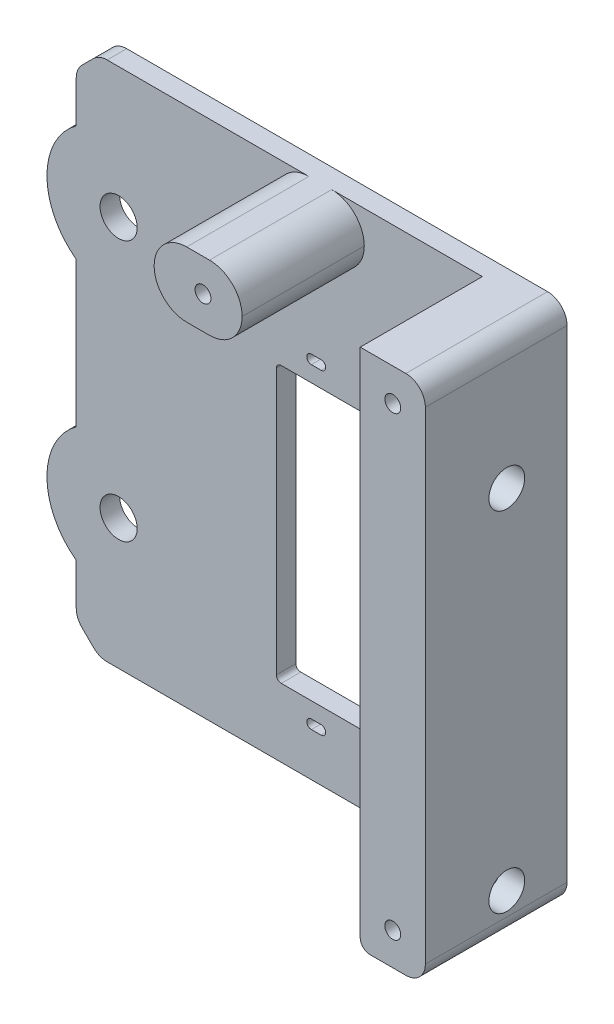
SolidWorks part; units mm, degrees
ref_plane "Front Plane" through (0, 0, 0) normal (0, 0, 1) x (1, 0, 0)
ref_plane "Top Plane" through (0, 0, 0) normal (0, 1, 0) x (1, 0, 0)
ref_plane "Right Plane" through (0, 0, 0) normal (1, 0, 0) x (0, 0, -1)
sketch "Base" plane through (0, 0, 0) normal (0, 0, 1) x (1, 0, 0)
  line L1 (-29.1058, 40) -> (-29.1058, -40)
  line L4 (-17.7758, -40) -> (43.2242, -40)
  line L8 (-22.6058, 20) -> (-22.6058, -20) construction
  line L9 (12.7242, 15.875) -> (12.7242, -32.625) construction
  line L10 (23.8492, 12.75) -> (1.5992, 12.75)
  line L11 (23.8492, 12.75) -> (23.8492, -29.5)
  line L12 (23.8492, -29.5) -> (1.5992, -29.5)
  line L13 (1.5992, 12.75) -> (1.5992, -29.5)
  line L14 (33.2242, 30) -> (33.2242, -30) construction
  line L15 (33.2242, 1) -> (43.2242, 1) construction
  line L16 (43.2242, 40) -> (43.2242, -40)
  line L18 (-17.7758, -40) -> (-29.1058, -40)
  line L19 (33.2242, -30) -> (33.2242, -40) construction
  line L20 (33.2242, 30) -> (43.2242, 40) construction
  line L21 (-29.1058, 40) -> (43.2242, 40)
  line L22 (7.7242, -32.625) -> (17.7242, -32.625)
  line L24 (33.2242, 30) -> (1.5992, 30) construction
  line L25 (1.5992, 30) -> (1.5992, 40) construction
  line L26 (1.5992, -40) -> (1.5992, -30) construction
  line L27 (1.5992, -30) -> (33.2242, -30) construction
  line L28 (7.7242, 15.875) -> (17.7242, 15.875)
  circle A0 centre (12.7242, -20) radius 17.5 construction
  point P2 (30.2242, -20)
  point P7 (24.1741, 0)
  point P9 (12.7242, -40)
  point P10 (-29.1058, 0)
  point P11 (-22.6058, -20)
  point P12 (-22.6058, 20)
  point P15 (-22.6058, 0)
  point P20 (12.7242, 12.75)
  point P22 (23.8492, -8.375)
  point P23 (12.7242, 20)
  point P24 (-22.6058, -20)
  point P25 (-22.6058, 20)
  point P26 (12.7242, 15.875)
  point P27 (12.7242, -32.625)
  point P30 (12.7242, -8.375)
  point P31 (12.7242, -20)
  point P33 (12.7242, -2.5)
  point P41 (38.2242, -35)
  point P43 (38.2242, 35)
  point P44 (9.0992, 35)
  point P45 (1.5992, 35)
  point P46 (38.2242, 1)
  point P47 (33.2242, -35)
  point P48 (7.7242, -32.625)
  point P49 (17.7242, -32.625)
  point P50 (7.7242, 15.875)
  point P51 (17.7242, 15.875)
  dimension "D11" = 35
  dimension "D2" = 42.25
  dimension "D1" = 22.25
  dimension "D4" = 35.33
  dimension "D9" = 48.5
  dimension "D3" = 40
  dimension "D10" = 9.5
  dimension "D5" = 6.5
  dimension "D14" = 10
  dimension "D7" = 80
  dimension "D8" = 10
  dimension "D12" = 3.5
  dimension "D6" = 3
  dimension "D13" = 7.5
  dimension "D15" = 10
sketch "Hole_sketch" plane through (0, 0, 0) normal (0, 0, 1) x (1, 0, 0)
  point P0 (-22.6058, -20)
  point P2 (-22.6058, 20)
  point P4 (12.7242, 15.875)
  point P6 (12.7242, -32.625)
extrude "Main" add sketch "Base" along normal blind 3 contours L18 L4 L16 L1 L13 L10 L11 L12 | L21 region at (7.0592, 38.9215, 0)
hole_wizard "Gear Axis Holes" positions "Sketch9" profile "Sketch8" hole size "Ø5.7" standard "ANSI Metric" end condition through all
sketch "Sketch9" plane through (0, 0, 3) normal (0, 0, -1) x (-1, 0, 0)
  point P0 (22.6058, -20)
  point P3 (22.6058, 20)
sketch "Sketch8" plane through (-22.6058, -20, 3) normal (1, 0, 0) x (0, -1, 0)
  line L0 (0, 0) -> (0, 3)
  line L1 (0, 3) -> (2.85, 3)
  line L2 (2.85, 3) -> (2.85, 0)
  line L5 (2.85, 0) -> (0, 0)
  line L11 (0, -6.35) -> (0, 107.95) construction
  dimension "Thru Hole Dia." = 5.7
  dimension "Thru Hole Depth" = 3
hole_wizard "M1.6 Clearance Hole1" positions "Sketch11" profile "Sketch10" hole size "M1.6" standard "ANSI Metric" end condition through all
sketch "Sketch11" plane through (0, 0, 3) normal (0, 0, 1) x (1, 0, 0)
  point P7 (17.7242, -32.625)
  point P9 (7.7242, -32.625)
  point P11 (7.7242, 15.875)
  point P13 (17.7242, 15.875)
sketch "Sketch10" plane through (17.7242, -32.625, 3) normal (1, 0, 0) x (0, -1, 0)
  line L0 (0, 0) -> (0, 3)
  line L1 (0, 3) -> (0.7, 3)
  line L2 (0.7, 3) -> (0.7, 0)
  line L5 (0.7, 0) -> (0, 0)
  line L11 (0, -6.35) -> (0, 107.95) construction
  dimension "Thru Hole Dia." = 1.4
  dimension "Thru Hole Depth" = 3
sketch "Sketch13" plane through (0, 0, 3) normal (0, 0, 1) x (1, 0, 0)
  line L10 (33.2242, 30) -> (33.2242, -30) construction
  line L11 (33.2242, 30) -> (1.5992, 30) construction
  line L12 (1.5992, 30) -> (1.5992, 40) construction
  line L13 (-29.1058, 40) -> (43.2242, 40) construction
  line L15 (43.2242, 40) -> (43.2242, -40) construction
  line L17 (33.2242, 30) -> (33.2242, 1)
  line L18 (33.2242, 30) -> (1.5992, 30)
  line L19 (1.5992, 30) -> (1.5992, 40)
  line L20 (1.5992, 40) -> (43.2242, 40)
  line L21 (43.2242, 40) -> (43.2242, 1)
  line L22 (33.2242, -30) -> (33.2242, -40) construction
  line L23 (-17.7758, -40) -> (43.2242, -40) construction
  line L24 (33.2242, -30) -> (33.2242, -40)
  line L25 (33.2242, 30) -> (33.2242, -30)
  line L26 (33.2242, -40) -> (43.2242, -40)
  line L27 (43.2242, 40) -> (43.2242, -40)
  line M42 (-29.1058, -40) -> (43.2242, -40)
  line M44 (43.2242, 40) -> (-29.1058, 40)
  line M60 (43.2242, -40) -> (43.2242, 40)
extrude "Boss-Extrude1" add sketch "Sketch13" along normal blind 18.75 contours L17 L25 L24 L19 L18 M42 M60 M44 region at (17.4117, 30.9018, 3)
fillet "Fillet2" radius 0.75 4 edges at (23.8492, -29.5, 1.5) (1.5992, -29.5, 1.5) (23.8492, 12.75, 1.5) (1.5992, 12.75, 1.5)
fillet "Fillet4" radius 5 3 edges at (1.5992, 30, 12.375) (33.2242, 30, 12.375)
fillet "Fillet8" radius 1.5 1 edges
sketch "Sketch21" plane through (0, 0, 3) normal (0, 0, 1) x (1, 0, 0)
  line L0 (-29.1058, 40) -> (-29.1058, -40) construction
  line L1 (-29.1058, 28.8741) -> (-29.1058, 11.1259)
  line L2 (-29.1058, -11.1259) -> (-29.1058, -28.8741)
  arc A0 (-29.1058, -11.1259) -> (-29.1058, -28.8741) centre (-22.6058, -20) ccw
  arc A1 (-29.1058, 28.8741) -> (-29.1058, 11.1259) centre (-22.6058, 20) ccw
  dimension "D1" = 22
extrude "Boss-Extrude2" add sketch "Sketch21" against normal up to surface (3 mm away) up to face at (18.4242, -32.625, 0)
chamfer "Chamfer1" distance 3.5 angle 45 2 edges at (-29.1058, -40, 1.5) (-29.1058, 40, 1.5)
fillet "Fillet6" radius 3 6 edges at (-25.6058, -40, 1.5) (-29.1058, -36.5, 1.5) (-29.1058, 36.5, 1.5) (-25.6058, 40, 1.5) (43.2242, 40, 10.875) (43.2242, -40, 10.875)
sketch "Sketch14" plane through (0, 0, 3) normal (0, 0, 1) x (1, 0, 0)
  line L0 (8.4742, -32.625) -> (6.9742, -32.625) construction
  line L1 (8.4742, -33.325) -> (6.9742, -33.325)
  line L2 (8.4742, -31.925) -> (6.9742, -31.925)
  line L3 (18.4742, -32.625) -> (16.9742, -32.625) construction
  line L4 (7.7242, -32.625) -> (17.7242, -32.625) construction
  line L5 (18.4742, -33.325) -> (16.9742, -33.325)
  line L6 (18.4742, -31.925) -> (16.9742, -31.925)
  line L7 (-1.3922, -8.375) -> (26.8405, -8.375) construction
  line L8 (8.4742, 15.875) -> (6.9742, 15.875) construction
  line L9 (8.4742, 16.575) -> (6.9742, 16.575)
  line L10 (8.4742, 15.175) -> (6.9742, 15.175)
  line L11 (18.4742, 15.875) -> (16.9742, 15.875) construction
  line L12 (18.4742, 16.575) -> (16.9742, 16.575)
  line L13 (18.4742, 15.175) -> (16.9742, 15.175)
  arc A0 (8.4742, -33.325) -> (8.4742, -31.925) centre (8.4742, -32.625) ccw
  arc A1 (6.9742, -31.925) -> (6.9742, -33.325) centre (6.9742, -32.625) ccw
  arc A2 (18.4742, -33.325) -> (18.4742, -31.925) centre (18.4742, -32.625) ccw
  arc A3 (16.9742, -31.925) -> (16.9742, -33.325) centre (16.9742, -32.625) ccw
  circle A6 centre (17.7242, -32.625) radius 0.7 construction
  arc A7 (8.4742, 16.575) -> (8.4742, 15.175) centre (8.4742, 15.875) cw
  arc A8 (6.9742, 15.175) -> (6.9742, 16.575) centre (6.9742, 15.875) cw
  arc A9 (18.4742, 16.575) -> (18.4742, 15.175) centre (18.4742, 15.875) cw
  arc A10 (16.9742, 15.175) -> (16.9742, 16.575) centre (16.9742, 15.875) cw
  point P2 (7.7242, -32.625)
  point P8 (17.7242, -32.625)
  point P26 (7.7242, 15.875)
  point P33 (17.7242, 15.875)
  dimension "D1" = 1.5
extrude "Cut-Extrude1" cut sketch "Sketch14" against normal through all
hole_wizard "#2 Clearance Hole1" positions "Sketch16" profile "Sketch15" hole size "#2" standard "ANSI Inch" end condition through all
sketch "Sketch16" plane through (0, 0, 21.75) normal (0, 0, 1) x (1, 0, 0)
  point P1 (9.0992, 35)
  point P3 (38.2242, 35)
  point P5 (38.2242, -35)
sketch "Sketch15" plane through (9.0992, 35, 21.75) normal (1, 0, 0) x (0, -1, 0)
  line L0 (0, 0) -> (0, 21.75)
  line L1 (0, 21.75) -> (1.2192, 21.75)
  line L2 (1.2192, 21.75) -> (1.2192, 0)
  line L5 (1.2192, 0) -> (0, 0)
  line L11 (0, -6.35) -> (0, 107.95) construction
  dimension "Thru Hole Dia." = 2.4384
  dimension "Thru Hole Depth" = 21.75
sketch "Sketch17" plane through (33.2242, 0, 0) normal (-1, 0, 0) x (0, 0, 1)
  line L1 (3, -38.5) -> (21.75, -38.5) construction
  line L2 (14.25, -38.5) -> (14.25, 25) construction
  line L3 (21.75, 25) -> (3, 25) construction
  line L4 (21.75, 25) -> (21.75, -38.5) construction
  line L5 (9.25, 20) -> (9.25, -33.5) construction
  line L6 (3, 35.2574) -> (3, 28.8741) construction
  line L7 (3, 35.2574) -> (3, 28.8741) construction
  line L8 (9.25, 20) -> (9.25, 25) construction
  line L9 (9.25, -33.5) -> (9.25, -38.5) construction
  point P0 (9.25, 20)
  point P1 (9.25, -33.5)
  point P2 (12.375, -38.5)
  point P13 (9.25, -6.75)
  point P16 (3, 32.0657)
  dimension "D1" = 5
  dimension "D2" = 7.5
  dimension "D3" = 5
hole_wizard "M5 Clearance Hole1" positions "Sketch19" profile "Sketch18" hole size "M5" standard "ANSI Metric" end condition through all
sketch "Sketch19" plane through (33.2242, 0, 0) normal (-1, 0, 0) x (0, 0, 1)
  point P1 (9.25, 20)
  point P3 (9.25, -33.5)
sketch "Sketch18" plane through (33.2242, 20, 9.25) normal (0, 1, 0) x (0, 0, 1)
  line L0 (0, 0) -> (0, 10)
  line L1 (0, 10) -> (2.75, 10)
  line L2 (2.75, 10) -> (2.75, 0)
  line L5 (2.75, 0) -> (0, 0)
  line L11 (0, -6.35) -> (0, 107.95) construction
  dimension "Thru Hole Dia." = 5.5
  dimension "Thru Hole Depth" = 10
sketch "Sketch20" plane through (0, 0, 21.75) normal (0, 0, 1) x (1, 0, 0)
  line L0 (15.0992, 25) -> (15.0992, 40)
  line L2 (40.2242, 40) -> (6.5992, 40) construction
  line L3 (15.0992, 40) -> (33.2242, 40)
  line L4 (33.2242, 40) -> (33.2242, 25)
  line L5 (33.2242, 25) -> (15.0992, 25)
  line L7 (33.2242, 25) -> (33.2242, -38.5) construction
  dimension "D1" = 13.5
extrude "Cut-Extrude2" cut sketch "Sketch20" against normal up to surface (18.75 mm away) up to face at (17.7242, 15.875, 3)
fillet "Fillet7" radius 5 2 edges at (15.0992, 40, 12.375) (15.0992, 30, 12.375)
equation "\"D_gear-axes\"= 40mm"
equation "\"D_gear-servo\"= 35mm"
equation "\"W_servo\"= 41.5mm"
equation "\"W_servo-center\"= 9.50mm"
equation "\"D1@Base\"=\"L_servo\"+0.75"
equation "\"D2@Base\"=\"W_servo\"+0.75"
equation "\"L_servo\"= 21.5mm"
equation "\"D4@Base\"=\"D_gear-servo\" + 0.33"
equation "\"D9@Base\"=\"D_servo-holes\""
equation "\"D_servo-holes\"= 48.5mm"
equation "\"D3@Base\"=\"D_gear-axes\""
equation "\"D10@Base\"=\"W_servo-center\""
